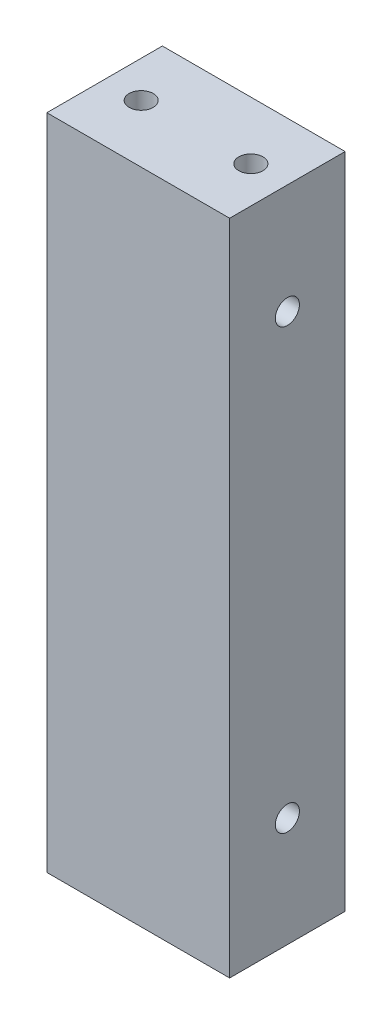
SolidWorks part; units mm, degrees
ref_plane "Front Plane" through (0, 0, 0) normal (0, 0, 1) x (1, 0, 0)
ref_plane "Top Plane" through (0, 0, 0) normal (0, 1, 0) x (1, 0, 0)
ref_plane "Right Plane" through (0, 0, 0) normal (1, 0, 0) x (0, 0, -1)
sketch "Sketch1" plane through (0, 0, 0) normal (0, 0, 1) x (1, 0, 0)
  line L1 (-12.5, -45) -> (12.5, -45)
  line L2 (-12.5, -45) -> (-12.5, 45)
  line L3 (-12.5, 45) -> (12.5, 45)
  line L4 (12.5, -45) -> (12.5, 45)
  line L5 (-12.5, -45) -> (12.5, 45) construction
  line L6 (-12.5, 45) -> (12.5, -45) construction
  point P0 (0, 0)
  dimension "D1" = 25
  dimension "D2" = 90
extrude "Boss-Extrude1" add sketch "Sketch1" along normal blind 15.8
hole_wizard "M4x0.7 Tapped Hole2" positions "Sketch5" profile "Sketch6" tap size "M4x0.7" standard "ANSI Metric"
sketch "Sketch5" plane through (12.5, 0, 0) normal (1, 0, 0) x (0, 0, -1)
  line L0 (-7.9, 30) -> (-7.9, -30)
  line L1 (-15.8, 45) -> (0, 45) construction
  point P0 (-7.9, 30)
  point P1 (-7.9, -30)
  point P4 (-7.9, 0)
  point P14 (-7.9, 45)
  dimension "D2" = 60
sketch "Sketch6" plane through (12.5, 30, 7.9) normal (0, 1, 0) x (0, 0, -1)
  line L0 (0, 0) -> (0, 11.0914)
  line L1 (0, 11.0914) -> (1.65, 10.1)
  line L2 (1.65, 10.1) -> (1.65, 0)
  line L5 (1.65, 0) -> (0, 0)
  line L10 (0, 11.0914) -> (-1.65, 10.1) construction
  line L11 (0, -6.35) -> (0, 107.95) construction
  dimension "Tap Drill Dia." = 3.3
  dimension "Tap Drill Depth" = 10.1
  dimension "Drill Angle" = 118
cosmetic thread "Hole Thread5" parameters "D1"=8, "D2"=4
cosmetic thread "Hole Thread6" parameters "D1"=8, "D2"=4
hole_wizard "M4x0.7 Tapped Hole1" positions "Sketch2" profile "Sketch4" tap size "M4x0.7" standard "ANSI Metric"
sketch "Sketch2" plane through (-12.5, 0, 0) normal (-1, 0, 0) x (0, 0, 1)
  line L0 (3.9, -30) -> (11.9, -30)
  line L2 (15.8, 45) -> (0, 45) construction
  point P0 (3.9, 30)
  point P2 (11.9, 30)
  point P4 (11.9, -30)
  point P6 (3.9, -30)
  point P19 (7.9, 45)
  point P20 (7.9, -30)
  dimension "D1" = 60
  dimension "D2" = 8
  dimension "D4" = 30
sketch "Sketch4" plane through (-12.5, 30, 3.9) normal (0, 1, 0) x (0, 0, 1)
  line L0 (0, 0) -> (0, 10.9914)
  line L1 (0, 10.9914) -> (1.65, 10)
  line L2 (1.65, 10) -> (1.65, 0)
  line L5 (1.65, 0) -> (0, 0)
  line L10 (0, 10.9914) -> (-1.65, 10) construction
  line L11 (0, -6.35) -> (0, 107.95) construction
  dimension "Tap Drill Dia." = 3.3
  dimension "Tap Drill Depth" = 10
  dimension "Drill Angle" = 118
cosmetic thread "Hole Thread1" parameters "D1"=8, "D2"=4
cosmetic thread "Hole Thread2" parameters "D1"=8, "D2"=4
cosmetic thread "Hole Thread3" parameters "D1"=8, "D2"=4
cosmetic thread "Hole Thread4" parameters "D1"=8, "D2"=4
hole_wizard "M4x0.7 Tapped Hole3" positions "Sketch7" profile "Sketch8" tap size "M4x0.7" standard "ANSI Metric"
sketch "Sketch7" plane through (0, -45, 0) normal (0, -1, 0) x (-1, 0, 0)
  line L0 (-7.5, -7.9) -> (7.5, -7.9)
  line L3 (12.5, -15.8) -> (12.5, 0) construction
  point P0 (-7.5, -7.9)
  point P1 (7.5, -7.9)
  point P4 (0, -7.9)
  point P16 (12.5, -7.9)
  dimension "D1" = 15
sketch "Sketch8" plane through (7.5, -45, 7.9) normal (1, 0, 0) x (0, 0, -1)
  line L0 (0, 0) -> (0, 11.0914)
  line L1 (0, 11.0914) -> (1.65, 10.1)
  line L2 (1.65, 10.1) -> (1.65, 0)
  line L5 (1.65, 0) -> (0, 0)
  line L10 (0, 11.0914) -> (-1.65, 10.1) construction
  line L11 (0, -6.35) -> (0, 107.95) construction
  dimension "Tap Drill Dia." = 3.3
  dimension "Tap Drill Depth" = 10.1
  dimension "Drill Angle" = 118
cosmetic thread "Hole Thread7" parameters "D1"=8, "D2"=4
cosmetic thread "Hole Thread8" parameters "D1"=8, "D2"=4
mirror "Mirror1" about plane through (0, 0, 0) normal (0, 1, 0) of "M4x0.7 Tapped Hole3"
cosmetic thread "Hole Thread9" parameters "D1"=8, "D2"=4
cosmetic thread "Hole Thread10" parameters "D1"=8, "D2"=4
